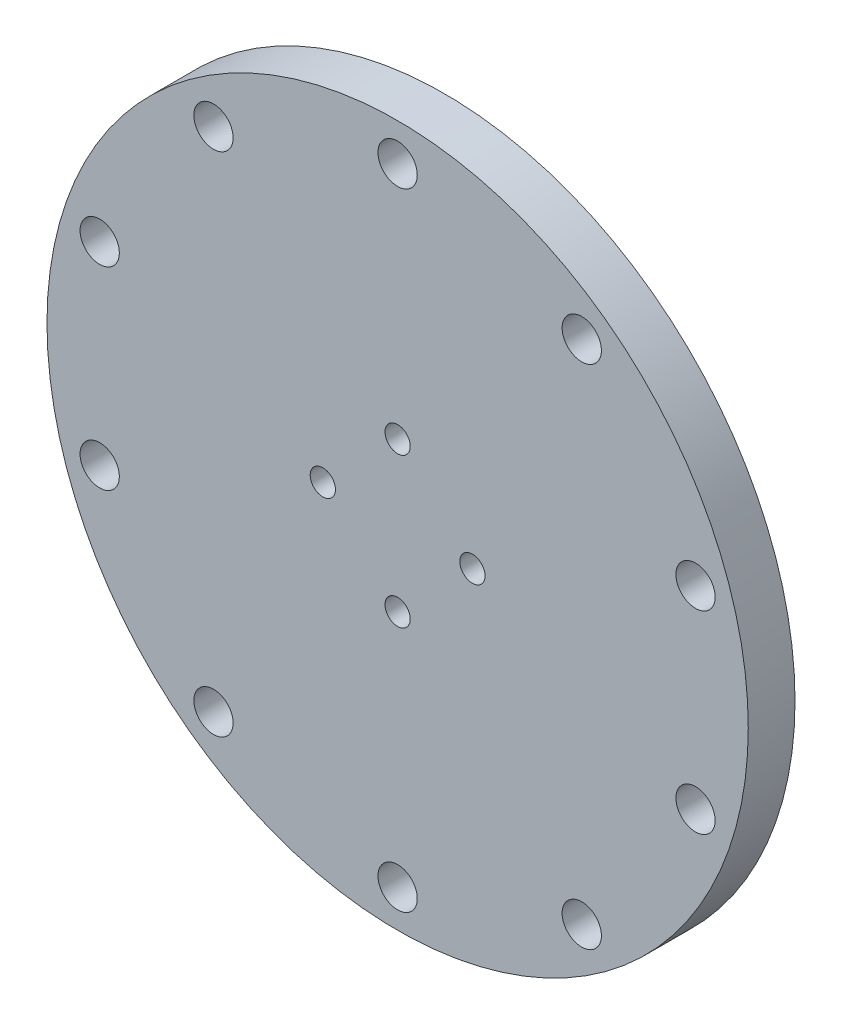
SolidWorks part; units mm, degrees
material "PETG_SRD"
ref_plane "Front Plane" through (0, 0, 0) normal (0, 0, 1) x (1, 0, 0)
ref_plane "Top Plane" through (0, 0, 0) normal (0, 1, 0) x (1, 0, 0)
ref_plane "Right Plane" through (0, 0, 0) normal (1, 0, 0) x (0, 0, -1)
sketch "Sketch1" plane through (0, 0, 0) normal (0, 0, 1) x (1, 0, 0)
  circle A0 centre (0, 0) radius 37.5
  circle A1 centre (0, 8) radius 1.35
  circle A2 centre (0, -8) radius 1.35
  circle A3 centre (8, 0) radius 1.35
  circle A4 centre (-8, 0) radius 1.35
  circle A5 centre (0, 0) radius 8 construction
  circle A6 centre (0, 0) radius 33.5 construction
  circle A7 centre (0, 33.5) radius 2.1
  circle A8 centre (19.6908, 27.1021) radius 2.1
  circle A9 centre (31.8604, 10.3521) radius 2.1
  circle A10 centre (31.8604, -10.3521) radius 2.1
  circle A11 centre (19.6908, -27.1021) radius 2.1
  circle A12 centre (0, -33.5) radius 2.1
  circle A17 centre (-19.6908, -27.1021) radius 2.1
  circle A18 centre (-31.8604, -10.3521) radius 2.1
  circle A19 centre (-31.8604, 10.3521) radius 2.1
  circle A20 centre (-19.6908, 27.1021) radius 2.1
  dimension "D1" = 2.7
  dimension "D2" = 16
  dimension "D3" = 75
  dimension "D4" = 67
  dimension "D5" = 4.2
  dimension "D6" = 10
extrude "Boss-Extrude1" add sketch "Sketch1" along normal blind 3
sketch "Sketch2" plane through (0, 0, 0) normal (0, 0, -1) x (-1, 0, 0)
  circle A0 centre (0, 0) radius 37.5
  circle A1 centre (0, 0) radius 29.5
  circle A24 centre (-19.6908, 27.1021) radius 2.1 construction
  circle A25 centre (-31.8604, 10.3521) radius 2.1 construction
  circle A26 centre (-31.8604, -10.3521) radius 2.1 construction
  circle A27 centre (-19.6908, -27.1021) radius 2.1 construction
  circle A28 centre (0, -33.5) radius 2.1 construction
  circle A29 centre (0, 33.5) radius 2.1 construction
  circle A30 centre (-19.6908, 27.1021) radius 2.1
  circle A31 centre (-31.8604, 10.3521) radius 2.1
  circle A32 centre (-31.8604, -10.3521) radius 2.1
  circle A33 centre (-19.6908, -27.1021) radius 2.1
  circle A34 centre (0, -33.5) radius 2.1
  circle A35 centre (0, 33.5) radius 2.1
  circle A36 centre (19.6908, -27.1021) radius 2.1 construction
  circle A37 centre (31.8604, -10.3521) radius 2.1 construction
  circle A38 centre (31.8604, 10.3521) radius 2.1 construction
  circle A39 centre (19.6908, 27.1021) radius 2.1 construction
  circle A40 centre (19.6908, -27.1021) radius 2.1
  circle A41 centre (31.8604, -10.3521) radius 2.1
  circle A42 centre (31.8604, 10.3521) radius 2.1
  circle A43 centre (19.6908, 27.1021) radius 2.1
  dimension "D1" = 59
  dimension "D2" = 75
extrude "Boss-Extrude2" add sketch "Sketch2" along normal blind 2
sketch "Sketch3" plane through (0, 0, 0) normal (0, 0, -1) x (-1, 0, 0)
  circle A1 centre (0, -8) radius 1.35 construction
  circle A2 centre (8, 0) radius 1.35 construction
  circle A3 centre (0, 8) radius 1.35 construction
  circle A4 centre (-8, 0) radius 1.35 construction
  circle A5 centre (0, -8) radius 1.35
  circle A6 centre (8, 0) radius 1.35
  circle A7 centre (0, 8) radius 1.35
  circle A8 centre (-8, 0) radius 1.35
  circle A13 centre (0, 0) radius 11.35
extrude "Boss-Extrude3" add sketch "Sketch3" along normal up to surface (2 mm away) up to face at (-33.9604, 10.3521, -2)
fillet "Fillet2" radius 10 1 edges at (11.35, 0, 0)
fillet "Fillet3" radius 10 1 edges at (-29.5, 0, 0)
